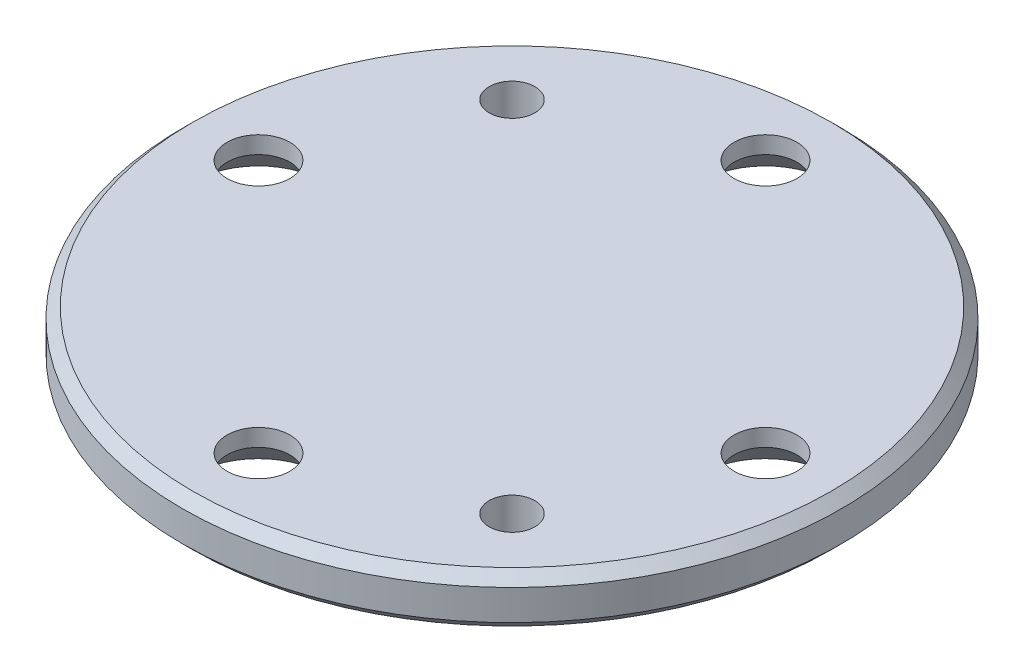
SolidWorks part; units mm, degrees
ref_plane "Front Plane" through (0, 0, 0) normal (0, 0, 1) x (1, 0, 0)
ref_plane "Top Plane" through (0, 0, 0) normal (0, 1, 0) x (1, 0, 0)
ref_plane "Right Plane" through (0, 0, 0) normal (1, 0, 0) x (0, 0, -1)
sketch "Sketch1" plane through (0, 0, 0) normal (0, 1, 0) x (1, 0, 0)
  line L0 (-17.6777, 17.6777) -> (0, 0) construction
  line L1 (0, 0) -> (17.6777, -17.6777) construction
  line L3 (0, -2.75) -> (0, 2.75) construction
  circle A0 centre (0, 0) radius 32.5
  circle A1 centre (0, 0) radius 25 construction
  circle A2 centre (0, 25) radius 3.1
  circle A3 centre (25, 0) radius 3.1
  circle A4 centre (0, -25) radius 3.1
  circle A5 centre (-25, 0) radius 3.1
  circle A6 centre (-17.6777, 17.6777) radius 2.25
  circle A7 centre (17.6777, -17.6777) radius 2.25
  point P15 (0, 0)
  dimension "D1" = 65
  dimension "D2" = 50
  dimension "D3" = 6.2
  dimension "D4" = 4
  dimension "D5" = 45
  dimension "D6" = 4.5
extrude "Boss-Extrude1" add sketch "Sketch1" along normal blind 5 contours A0 | A5 | A2 | A3 | A4 | A6 | A7
ref_axis "Axis1" through (-17.6777, 5, -17.6777) along (0, -1, 0)
ref_axis "Axis2" through (17.6777, 5, 17.6777) along (0, -1, 0)
chamfer "Chamfer1" distance 3.3 angle 45 4 edges at (0, 0, -21.9) (25, 0, 3.1) (0, 0, 28.1) (-25, 0, 3.1)
chamfer "Chamfer2" distance 1 angle 45 2 edges at (0, 5, 32.5) (0, 0, 32.5)
equation "\"1。5\"=2.53495"
